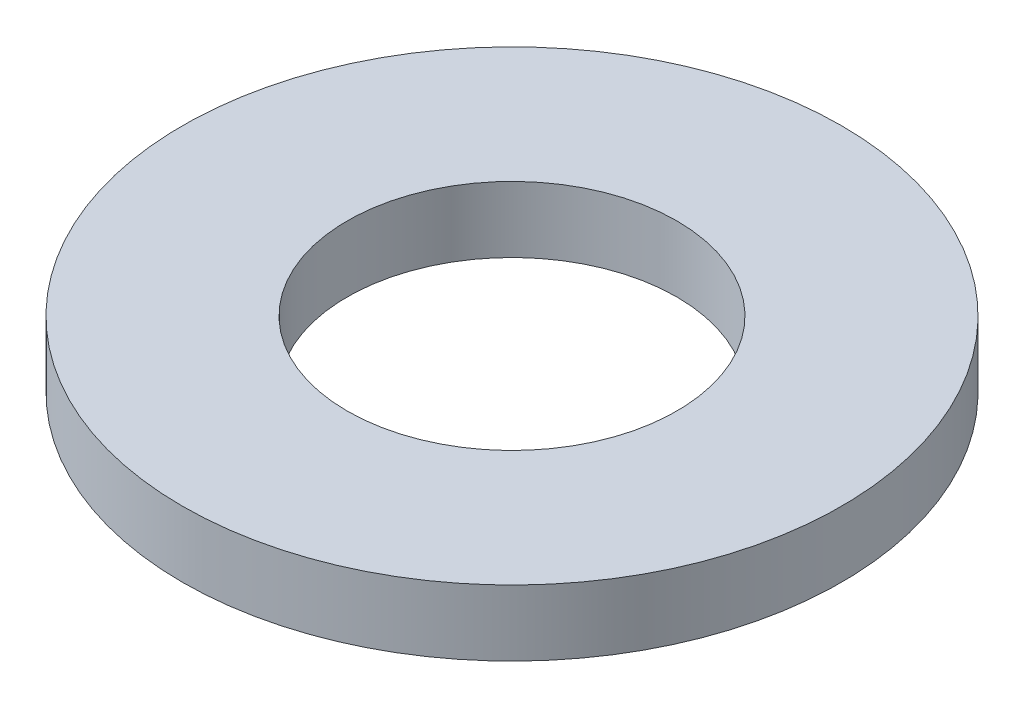
SolidWorks part; units mm, degrees
ref_plane "Front Plane" through (0, 0, 0) normal (0, 0, 1) x (1, 0, 0)
ref_plane "Top Plane" through (0, 0, 0) normal (0, 1, 0) x (1, 0, 0)
ref_plane "Right Plane" through (0, 0, 0) normal (1, 0, 0) x (0, 0, -1)
sketch "Sketch1" plane through (0, 0, 0) normal (0, 1, 0) x (1, 0, 0)
  circle A0 centre (0, 0) radius 60
  dimension "FLANGE_OD" = 120
extrude "Boss-Extrude1" add sketch "Sketch1" along normal blind 12
sketch "Sketch2" plane through (0, 0, 0) normal (0, 1, 0) x (1, 0, 0)
  circle A0 centre (0, 0) radius 30
  dimension "BORE_D" = 60
extrude "Cut-Extrude1" cut sketch "Sketch2" along normal through all
sketch "Sketch3" plane through (0, 12, 0) normal (0, 1, 0) x (1, 0, 0)
  circle A0 centre (0, 0) radius 18.2172 construction
  circle A1 centre (-18.2172, 0) radius 3.2686
  dimension "BOLT_D" = 6.5372
  dimension "BOLT_PCD" = 36.4343
extrude "Cut-Extrude2" cut sketch "Sketch3" against normal blind 11.0362 rebuild error yes
pattern_circular "CirPattern1" count 8 over 360 rebuild error yes
